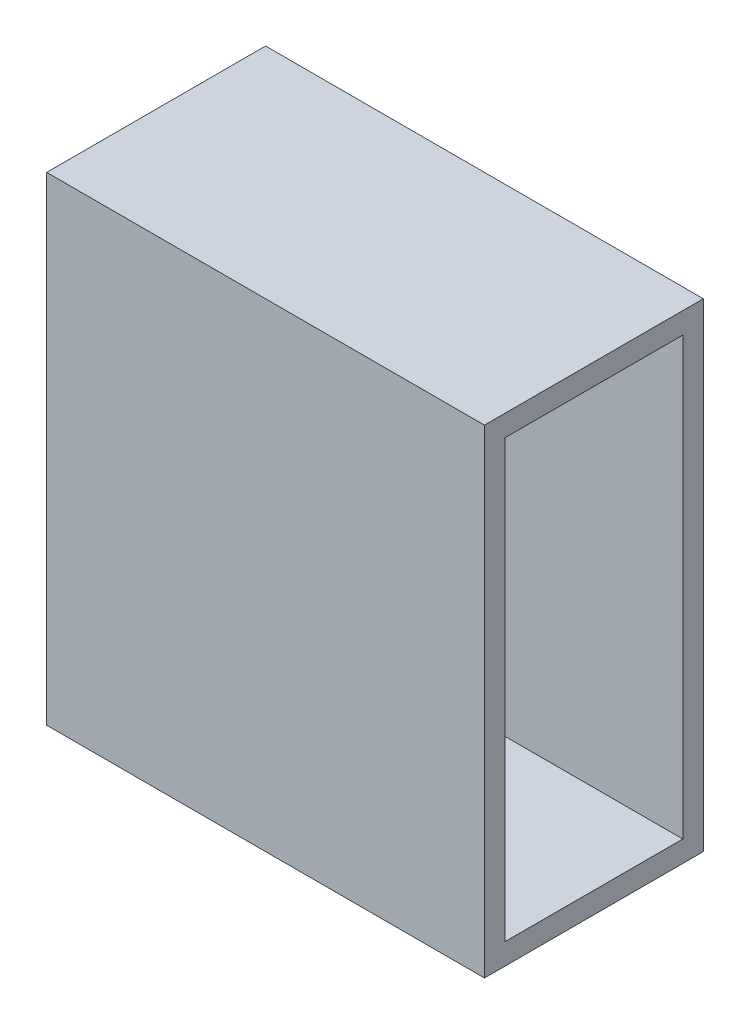
SolidWorks part; units mm, degrees
ref_plane "Front Plane" through (0, 0, 0) normal (1, 0, 0) x (0, 1, 0)
ref_plane "Top Plane" through (0, 0, 0) normal (0, 0, 1) x (0, 1, 0)
ref_plane "Right Plane" through (0, 0, 0) normal (0, 1, 0) x (-1, 0, 0)
sketch "Sketch1" plane through (0, 0, 0) normal (1, 0, 0) x (0, 1, 0)
  line L5 (-35, 8) -> (-29.25, 8) construction
  line L6 (-35, 16) -> (0, 16)
  line L11 (-35, 16) -> (-35, 0)
  line L12 (-35, 0) -> (0, 0)
  line L20 (0, 16) -> (0, 0)
  line L21 (-29.25, 14.5) -> (-5.75, 14.5)
  line L22 (-29.25, 14.5) -> (-29.25, 1.5)
  line L23 (-29.25, 1.5) -> (-5.75, 1.5)
  line L24 (-5.75, 14.5) -> (-5.75, 1.5)
  line L25 (-5.75, 8) -> (0, 8) construction
  line L26 (-17.5, 0) -> (-17.5, 1.5) construction
  line L27 (-17.5, 16) -> (-17.5, 14.5) construction
  line L29 (-33.45, 1.5) -> (-1.55, 1.5)
  line L30 (-33.45, 1.5) -> (-33.45, 14.5)
  line L31 (-33.45, 14.5) -> (-1.55, 14.5)
  line L32 (-1.55, 1.5) -> (-1.55, 14.5)
  dimension "D1" = 4.2
  dimension "D2" = 13
  dimension "D3" = 4.2
  dimension "D6" = 35
  dimension "D7" = 23.5
  dimension "D9" = 1.5
extrude "Boss-Extrude1" add sketch "Sketch1" along normal blind 26 contours L20 L6 L11 L12 L21 L24 L23 L22 region at (0, -17.5, 15.6152)
extrude "Boss-Extrude2" add sketch "Sketch1<3>" along normal blind 2 contours L31 L30 L29 L22 | L29 L32 L31 L24 region at (0, -31.35, 8) region at (0, -3.65, 8)
sketch "Sketch1<3>" plane through (0, 0, 0) normal (1, 0, 0) x (0, 1, 0) same geometry as "Sketch1"
sketch "Sketch2" plane through (26, 0, 0) normal (1, 0, 0) x (0, 1, 0)
  line L1 (-35, 16) -> (0, 16)
  line L2 (-35, 16) -> (-35, 0)
  line L3 (-35, 0) -> (0, 0)
  line L4 (0, 16) -> (0, 0)
sketch "Sketch3" plane through (0, 0, 0) normal (-1, 0, 0) x (0, -1, 0)
  line L1 (0, 16) -> (35, 16)
  line L2 (0, 16) -> (0, 0)
  line L3 (0, 0) -> (35, 0)
  line L4 (35, 16) -> (35, 0)
  line L5 (1.55, 14.5) -> (33.45, 14.5)
  line L6 (1.55, 14.5) -> (1.55, 1.5)
  line L7 (1.55, 1.5) -> (33.45, 1.5)
  line L8 (33.45, 14.5) -> (33.45, 1.5)
extrude "Boss-Extrude4" add sketch "Sketch3" along normal blind 4.5
sketch "Sketch5" plane through (-4.5, 0, 0) normal (-1, 0, 0) x (0, -1, 0)
  line L0 (35, 8) -> (29.25, 8) construction
  line L1 (0, 16) -> (35, 16)
  line L2 (0, 16) -> (0, 0)
  line L3 (0, 0) -> (35, 0)
  line L4 (35, 16) -> (35, 0)
  line L5 (29.25, 14.5) -> (29.25, 1.5) construction
  circle A0 centre (22.25, 8) radius 5.2
  dimension "D1" = 10.4
  dimension "D2" = 7
extrude "Boss-Extrude5" add sketch "Sketch5" along normal blind 1.5
